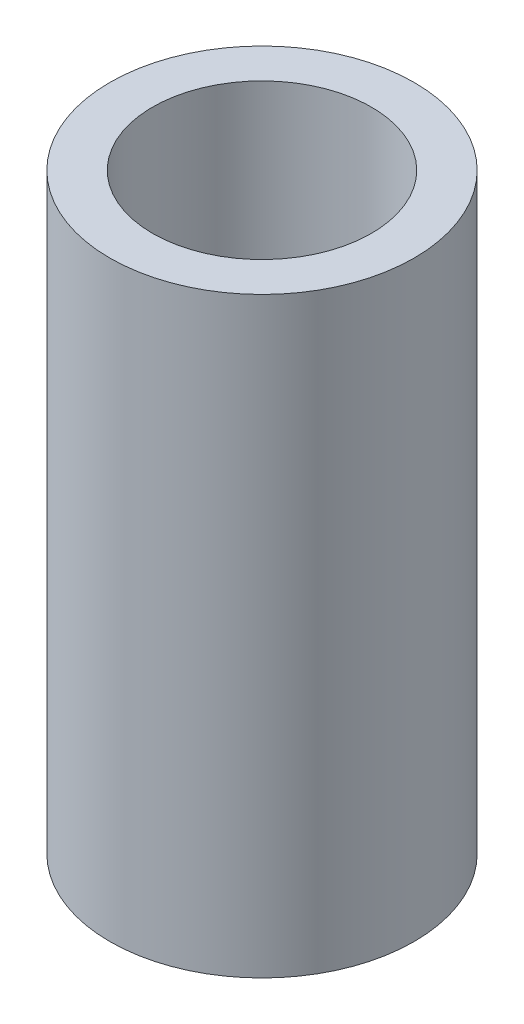
SolidWorks part; units mm, degrees
ref_plane "Front Plane" through (0, 0, 0) normal (0, 0, 1) x (1, 0, 0)
ref_plane "Top Plane" through (0, 0, 0) normal (0, 1, 0) x (1, 0, 0)
ref_plane "Right Plane" through (0, 0, 0) normal (1, 0, 0) x (0, 0, -1)
sketch "Sketch1" plane through (0, 0, 0) normal (0, 1, 0) x (1, 0, 0)
  circle A0 centre (0, 0) radius 22.5
  dimension "SLEEVE_OD" = 45
extrude "Boss-Extrude1" add sketch "Sketch1" along normal blind 87.5405
sketch "Sketch2" plane through (0, 0, 0) normal (0, 1, 0) x (1, 0, 0)
  circle A0 centre (0, 0) radius 16.1839
  dimension "BORE_D" = 32.3678
extrude "Cut-Extrude1" cut sketch "Sketch2" along normal through all
chamfer "Chamfer1" distance 3.2906 angle 60 rebuild error yes
